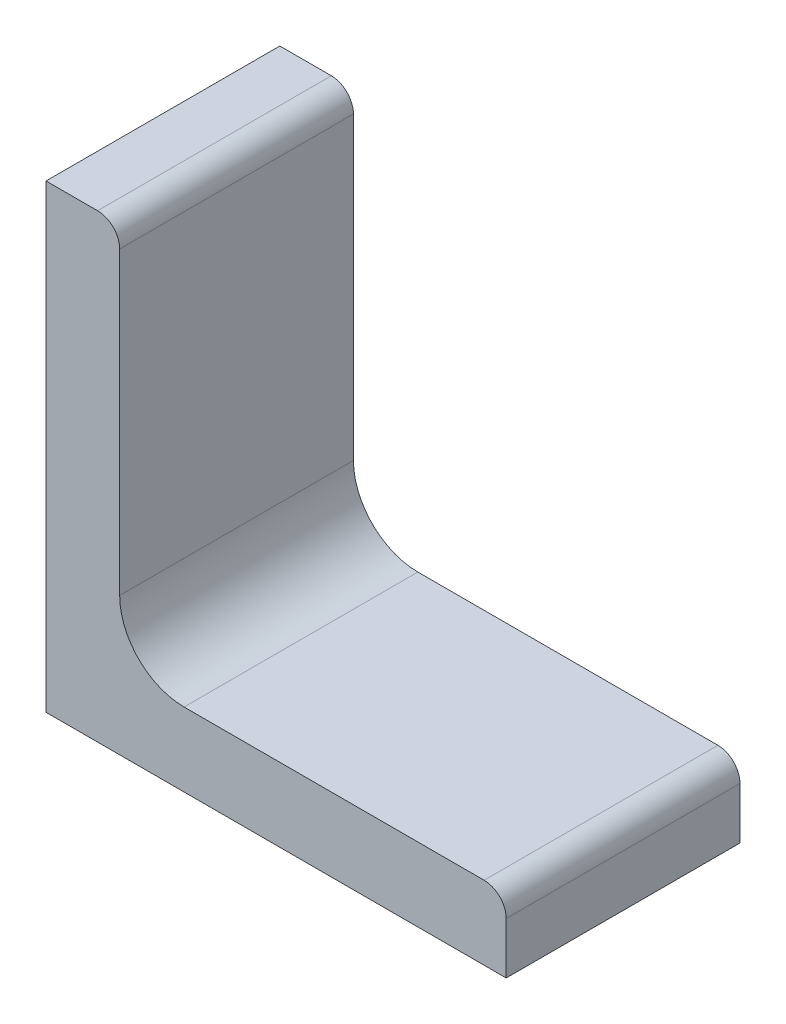
SolidWorks part; units mm, degrees
ref_plane "Front Plane" through (0, 0, 0) normal (0, 0, 1) x (1, 0, 0)
ref_plane "Top Plane" through (0, 0, 0) normal (0, 1, 0) x (1, 0, 0)
ref_plane "Right Plane" through (0, 0, 0) normal (1, 0, 0) x (0, 0, -1)
sketch "Sketch1" plane through (0, 0, 0) normal (0, 0, 1) x (1, 0, 0)
  line L1 (0, 0) -> (50, 0)
  line L2 (0, 0) -> (0, 50)
  line L3 (0, 50) -> (5.6, 50)
  line L4 (50, 0) -> (50, 5.6)
  line L6 (8, 47.6) -> (8, 15)
  line L7 (15, 8) -> (47.6, 8)
  arc A0 (8, 15) -> (15, 8) centre (15, 15) ccw
  arc A1 (5.6, 50) -> (8, 47.6) centre (5.6, 47.6) cw
  arc A2 (50, 5.6) -> (47.6, 8) centre (47.6, 5.6) ccw
  dimension "Radius_root" = 7
  dimension "Radius_toe" = 2.4
  dimension "Width" = 50
  dimension "Thickness" = 8
extrude "BaseSection" add sketch "Sketch1" along normal mid plane 25.4
